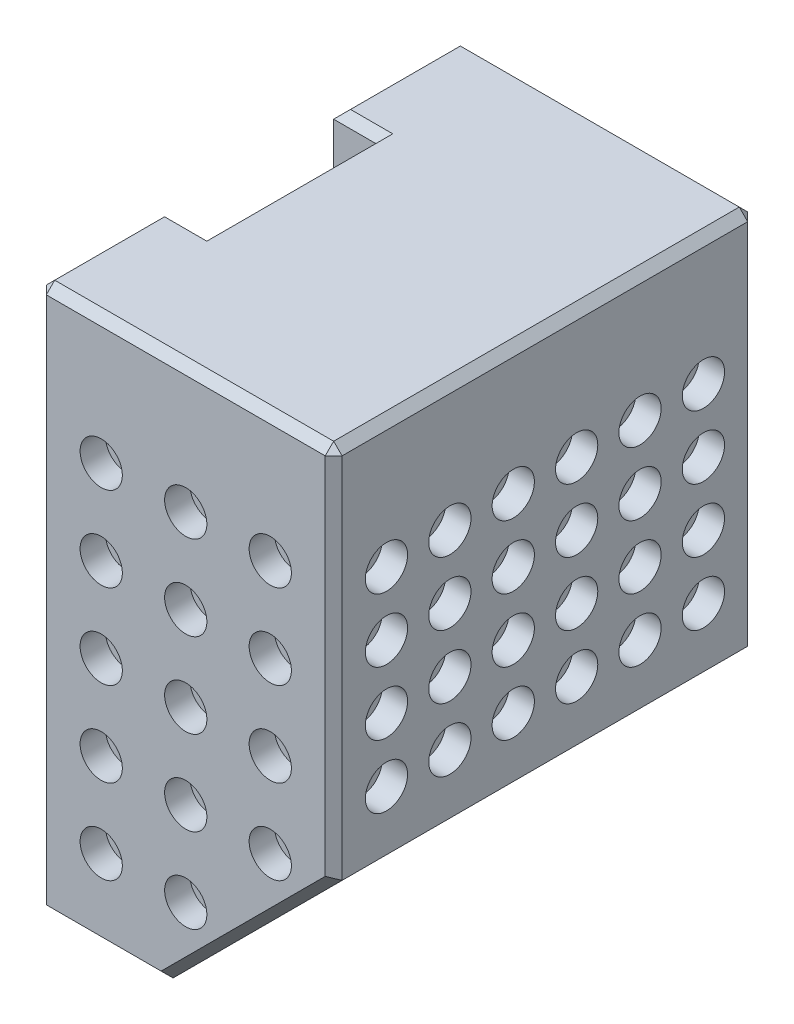
SolidWorks part; units mm, degrees
material "K110"
ref_plane "Front Plane" through (0, 0, 0) normal (0, 0, 1) x (1, 0, 0)
ref_plane "Top Plane" through (0, 0, 0) normal (0, 1, 0) x (1, 0, 0)
ref_plane "Right Plane" through (0, 0, 0) normal (1, 0, 0) x (0, 0, -1)
sketch "Sketch1" plane through (0, 0, 0) normal (0, 1, 0) x (1, 0, 0)
  line L1 (-17.5, -24.995) -> (17.5, -24.995)
  line L2 (-17.5, -24.995) -> (-17.5, 24.995)
  line L3 (-17.5, 24.995) -> (17.5, 24.995)
  line L4 (17.5, -24.995) -> (17.5, 24.995)
  line L5 (-17.5, -24.995) -> (17.5, 24.995) construction
  line L6 (-17.5, 24.995) -> (17.5, -24.995) construction
  point P0 (0, 0)
  dimension "D1" = 49.99
  dimension "D2" = 35
extrude "Boss-Extrude1" add sketch "Sketch1" against normal blind 64.5
sketch "Sketch2" plane through (0, 0, 24.995) normal (0, 0, 1) x (1, 0, 0)
  line L0 (-2.5, -64.5) -> (17.5, -44.5)
  line L1 (-17.5, -64.5) -> (17.5, -64.5) construction
  line L2 (17.5, -64.5) -> (17.5, 0) construction
  line L3 (17.5, -44.5) -> (17.5, -64.5)
  line L4 (17.5, -64.5) -> (-2.5, -64.5)
  dimension "D1" = 20
  dimension "D2" = 45
extrude "Cut-Extrude1" cut sketch "Sketch2" against normal up to next
sketch "Sketch3" plane through (-17.5, 0, 0) normal (-1, 0, 0) x (0, 0, 1)
  line L0 (-24.995, -64.5) -> (24.995, -64.5) construction
  line L1 (-7, -64.5) -> (7, -64.5)
  line L2 (-7, -64.5) -> (-7, -44.5)
  line L3 (-7, -44.5) -> (7, -44.5)
  line L4 (7, -64.5) -> (7, -44.5)
  line L5 (-24.995, -44.5) -> (24.995, -44.5) construction
  point P8 (0, -44.5)
  dimension "D1" = 14
  dimension "D2" = 20
extrude "Cut-Extrude2" cut sketch "Sketch3" against normal up to next
fillet "Fillet1" 2 edges at (0, -44.5, -7) (0, -44.5, 7) type full round first side face at (-5, -54.5, -7) second side face at (-5, -54.5, 7) middle face at (0, -44.5, 0)
sketch "Sketch4" plane through (0, 0, 0) normal (0, 1, 0) x (1, 0, 0)
  line L0 (-17.5, 0) -> (17.5, 0) construction
  line L1 (-17.5, 24.995) -> (-17.5, -24.995) construction
  line L2 (17.5, -24.995) -> (17.5, 24.995) construction
  line L4 (-17.5, -10) -> (-12.5, -10)
  line L5 (-17.5, -10) -> (-17.5, 10)
  line L6 (-17.5, 10) -> (-12.5, 10)
  line L7 (-12.5, -10) -> (-12.5, 10)
  dimension "D1" = 5
  dimension "D2" = 20
extrude "Cut-Extrude3" cut sketch "Sketch4" against normal blind 43
sketch "Sketch5" plane through (-17.5, 0, 0) normal (-1, 0, 0) x (0, 0, 1)
  line L0 (-10, -43) -> (-10, 0) construction
  line L1 (-15, -43) -> (15, -43)
  line L2 (-15, -43) -> (-15, -38)
  line L3 (-15, -38) -> (15, -38)
  line L4 (15, -43) -> (15, -38)
  line L5 (-10, -43) -> (10, -43) construction
  line L6 (10, -43) -> (10, 0) construction
  dimension "D1" = 5
  dimension "D2" = 5
  dimension "D3" = 5
extrude "Cut-Extrude4" cut sketch "Sketch5" against normal up to surface (5 mm away) up to face at (-12.5, -21.5, 0)
fillet "Fillet5" 2 edges at (-15, -43, -15) (-15, -38, -15) type full round first side face at (-15, -43, 0) second side face at (-15, -38, -12.5) middle face at (-15, -40.5, -15)
fillet "Fillet6" 2 edges at (-15, -43, 15) (-15, -38, 15) type full round first side face at (-15, -43, 1.25) second side face at (-15, -38, 12.5) middle face at (-15, -40.5, 15)
chamfer "Chamfer1" distance 1 angle 45 16 edges at (17.5, 0, 0) (17.5, -22.25, -24.995) (0, 0, -24.995) (7.5, -54.5, -24.995) (-10, -64.5, -24.995) (-17.5, -32.25, -24.995) (-17.5, 0, -17.4975) (-15, 0, -10) (-12.5, 0, 0) (-15, 0, 10) (-17.5, 0, 17.4975) (-10, -64.5, 24.995) (-17.5, -32.25, 24.995) (0, 0, 24.995) (17.5, -22.25, 24.995) (7.5, -54.5, 24.995)
sketch "Sketch6" plane through (0, 0, 24.995) normal (0, 0, 1) x (1, 0, 0)
  line L0 (-16.5, 0) -> (16.5, 0) construction
  line L1 (-17.5, -64.5) -> (-17.5, -1) construction
  circle A0 centre (-10, -15) radius 2.5
  dimension "D1" = 5
  dimension "D2" = 15
  dimension "D3" = 7.5
extrude "Cut-Extrude5" cut sketch "Sketch6" against normal blind 3
pattern_linear "LPattern1" count 3 spacing 10 along (1, 0, 0) count 5 spacing 10 along (0, -1, 0) skipping (2, 4) of "Cut-Extrude5"
sketch "Sketch9" plane through (17.5, 0, 0) normal (1, 0, 0) x (0, 0, -1)
  line L0 (-24.995, -44.0858) -> (-24.995, -1) construction
  line L1 (-23.995, 0) -> (23.995, 0) construction
  circle A0 centre (-18.745, -15) radius 2.5
  dimension "D1" = 5
  dimension "D2" = 6.25
  dimension "D3" = 15
extrude "Cut-Extrude20" cut sketch "Sketch9" against normal blind 3
pattern_linear "LPattern2" count 4 spacing 7.5 along (0, -1, 0) count 6 spacing 7.5 along (0, 0, -1) of "Cut-Extrude20"
sketch "Sketch10" plane through (-17.5, 0, 0) normal (-1, 0, 0) x (0, 0, 1)
  line L0 (-10, -1) -> (-23.995, -1) construction
  line L2 (-23.995, 0) -> (-11, 0) construction
  circle A0 centre (-16.9975, -15) radius 2.5
  point P7 (-16.9975, -1)
  dimension "D1" = 5
  dimension "D2" = 15
extrude "Cut-Extrude21" cut sketch "Sketch10" against normal blind 3
pattern_linear "LPattern3" count 7 spacing 7.5 along (0, -1, 0) count 2 spacing 35 along (0, 0, 1) of "Cut-Extrude21"
sketch "Sketch11" plane through (31, -31, 0) normal (0.7071, -0.7071, 0) x (0, 0, -1)
  line L0 (-24.995, -46.9619) -> (-24.995, -19.5061) construction
  line L2 (0, -19.0919) -> (-23.995, -19.0919) construction
  circle A0 centre (-18.745, -26.5919) radius 2.5
  dimension "D1" = 6.25
  dimension "D2" = 5
  dimension "D5" = 7.5
extrude "Cut-Extrude23" cut sketch "Sketch11" against normal blind 3
pattern_linear "LPattern5" count 6 spacing 7.5 along (0, 0, -1) count 3 spacing 7.5 along (-0.7071, -0.7071, 0) skipping (2, 0), (2, 1), (2, 2), (3, 0), (3, 1), (3, 2) of "Cut-Extrude23"
sketch "Sketch18" plane through (0, 0, -24.995) normal (0, 0, -1) x (-1, 0, 0)
  circle A0 centre (10, -15) radius 2.5
extrude "Cut-Extrude25" cut sketch "Sketch18" against normal blind 3
pattern_linear "LPattern7" count 3 spacing 10 along (1, 0, 0) count 5 spacing 10 along (0, -1, 0) of "Cut-Extrude25"
ref_plane "Plane1" [suppressed] through (31, -31, 0) normal (0.7071, -0.7071, 0) x (-0.7071, -0.7071, 0)
sketch "Sketch19" [suppressed] plane through (31, -31, 0) normal (0.7071, -0.7071, 0) x (0, 0, -1)
  line L0 (-25, -33.234) -> (25, -33.234)
  line L1 (-25, -19.0919) -> (-25, -47.3762) construction
  line L2 (25, -19.0919) -> (25, -47.3762) construction
  line L3 (0, -19.0919) -> (0, -33.234)
